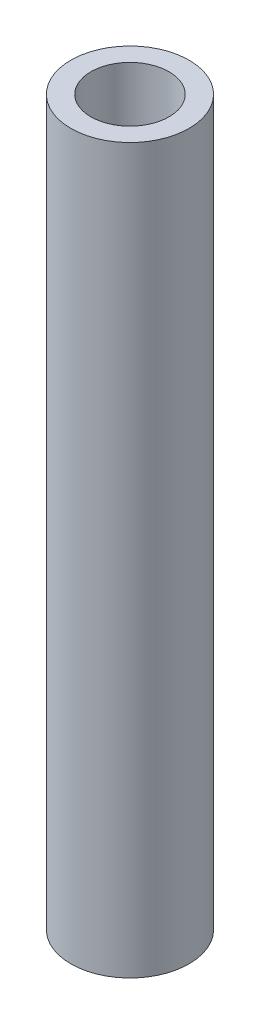
SolidWorks part; units mm, degrees
material "ABS"
ref_plane "Front Plane" through (0, 0, 0) normal (0, 0, 1) x (1, 0, 0)
ref_plane "Top Plane" through (0, 0, 0) normal (0, 1, 0) x (1, 0, 0)
ref_plane "Right Plane" through (0, 0, 0) normal (1, 0, 0) x (0, 0, -1)
sketch "Sketch1" plane through (0, 0, 0) normal (0, 1, 0) x (1, 0, 0)
  circle A0 centre (0, 0) radius 4.425
  circle A1 centre (0, 0) radius 2.925
  dimension "D1" = 8.85
  dimension "D2" = 1.5
extrude "Boss-Extrude1" add sketch "Sketch1" against normal up to surface (54.15 mm away)
